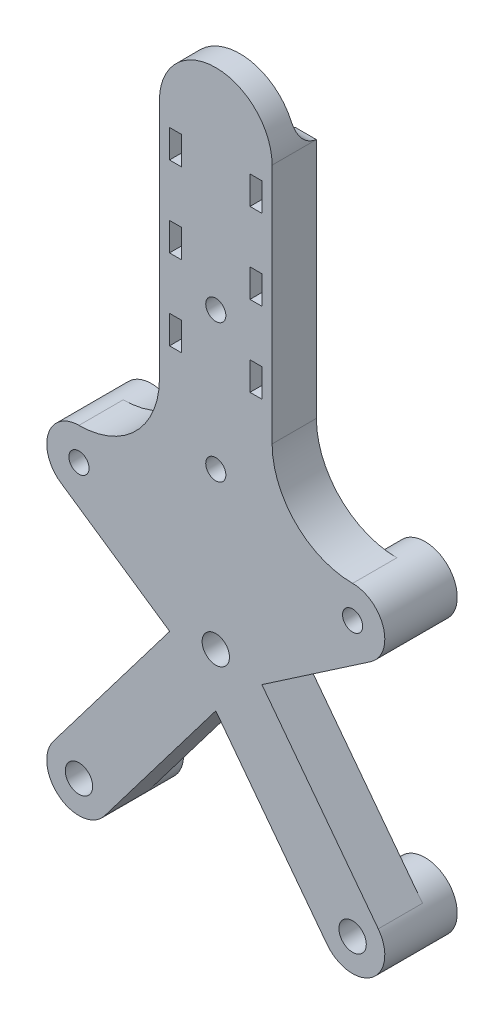
SolidWorks part; units mm, degrees
note: The reader was unsure of these and kept them because the rebuilt part matched: shared geometry of "Sketch1<3>".
ref_plane "Front Plane" through (0, 0, 0) normal (0, 0, 1) x (1, 0, 0)
ref_plane "Top Plane" through (0, 0, 0) normal (0, 1, 0) x (1, 0, 0)
ref_plane "Right Plane" through (0, 0, 0) normal (1, 0, 0) x (0, 0, -1)
sketch "Sketch1" plane through (0, 0, 0) normal (0, 0, 1) x (1, 0, 0)
  line L0 (-17, -11.2005) -> (0, 11.2005) construction
  line L1 (-17, -11.2005) -> (-11.9786, -11.2005) construction
  line L2 (-17, -11.2005) -> (-17, -4.5837) construction
  line L3 (-17, 22.7995) -> (17, 22.7995) construction
  line L4 (17, -11.2005) -> (17, -4.5837) construction
  line L5 (0, 11.2005) -> (-17, 22.7995) construction
  line L6 (17, -11.2005) -> (0, 11.2005) construction
  line L7 (0, 11.2005) -> (17, 22.7995) construction
  line L8 (-13.8137, -13.6186) -> (0, 4.5837)
  line L14 (20.1863, -8.7824) -> (5.7296, 10.2674)
  line L16 (-20.1863, -8.7824) -> (-5.7296, 10.2674)
  line L19 (-17, 26.7995) -> (17, 26.7995)
  line L22 (13.8137, -13.6186) -> (0, 4.5837)
  line L25 (5.7296, 10.2674) -> (19.2544, 19.4953)
  line L26 (17, 17.9571) -> (17, 22.7995) construction
  line L27 (-5.7296, 10.2674) -> (-19.2544, 19.4953)
  line L29 (11.9786, -11.2005) -> (17, -11.2005) construction
  line L30 (3.3084, 13.4578) -> (3.1863, 13.6186)
  line L31 (20.1863, -8.7824) -> (3.1863, 13.6186) construction
  line L34 (-3.3084, 13.4578) -> (-3.1863, 13.6186)
  line L35 (-20.1863, -8.7824) -> (-3.1863, 13.6186) construction
  line L36 (0, 26.7995) -> (0, 66.7995) construction
  line L37 (-13.8137, -13.6186) -> (3.1863, 8.7824) construction
  line L38 (7, 26.7995) -> (7, 66.7995)
  line L39 (13.8137, -13.6186) -> (-3.1863, 8.7824) construction
  line L40 (-7, 26.7995) -> (-7, 66.7995)
  line L41 (-17, 17.9571) -> (-17, 22.7995) construction
  arc A0 (-13.8137, -13.6186) -> (-20.1863, -8.7824) centre (-17, -11.2005) cw
  arc A1 (3.3042, 13.4549) -> (3.1863, 13.6186) centre (0, 11.2005) ccw
  arc A2 (-17, -15.2005) -> (-20.1863, -8.7824) centre (-17, -11.2005) cw
  arc A3 (17, -15.2005) -> (20.1863, -8.7824) centre (17, -11.2005) ccw
  arc A4 (-13.8137, -13.6186) -> (-21, -11.2005) centre (-17, -11.2005) cw
  arc A5 (-14.7456, 26.1037) -> (-21, 22.7995) centre (-17, 22.7995) ccw
  arc A6 (-19.2544, 19.4953) -> (-17, 26.7995) centre (-17, 22.7995) cw
  arc A7 (19.2544, 19.4953) -> (17, 26.7995) centre (17, 22.7995) ccw
  arc A8 (21, -11.2005) -> (13.8137, -13.6186) centre (17, -11.2005) cw
  arc A9 (21, 22.7995) -> (14.7456, 26.1037) centre (17, 22.7995) ccw
  arc A10 (3.1863, 13.6186) -> (3.3042, 13.4549) centre (0, 11.2005) cw
  arc A11 (-14.7456, 26.1037) -> (-19.2544, 19.4953) centre (-17, 22.7995) ccw
  arc A12 (20.1863, -8.7824) -> (13.8137, -13.6186) centre (17, -11.2005) cw
  arc A15 (19.2544, 19.4953) -> (14.7456, 26.1037) centre (17, 22.7995) ccw
  circle A16 centre (-17, -11.2005) radius 4
  arc A17 (-3.3042, 13.4549) -> (-3.1863, 13.6186) centre (0, 11.2005) cw
  arc A18 (-3.1863, 13.6186) -> (-3.3042, 13.4549) centre (0, 11.2005) ccw
  circle A19 centre (17, -11.2005) radius 4
  circle A20 centre (17, 22.7995) radius 4
  circle A21 centre (-17, 22.7995) radius 4
  arc A23 (7, 66.7995) -> (-7, 66.7995) centre (0, 66.7995) ccw
  point P0 (17, -11.2005)
  point P1 (-17, -11.2005)
  point P2 (0, 11.2005)
  point P5 (17, 22.7995)
  point P6 (-17, 22.7995)
  dimension "D6" = 40
  dimension "D7" = 34
  dimension "D8" = 34
  dimension "D2" = 4
  dimension "D3" = 4
  dimension "D4" = 7
  dimension "D5" = 7
  dimension "D1" = 2
extrude "Boss-Extrude1" add sketch "Sketch1" along normal blind 3
extrude "Boss-Extrude2" add sketch "Sketch1<3>" against normal blind 6 contours A6 A21 A5 | A9 A20 A7 | A3 A19 A8 | A0 A16
sketch "Sketch1<3>" plane through (0, 0, 0) normal (0, 0, 1) x (1, 0, 0) same geometry as "Sketch1"
hole_wizard "Tap Drill for M3x0.5 Tap1" positions "Sketch2" profile "Sketch3" hole size "M3x0.5" standard "ANSI Metric"
sketch "Sketch2" plane through (0, 0, -6) normal (0, 0, -1) x (-1, 0, 0)
  point P0 (17, 22.7995)
  point P3 (-17, 22.7995)
sketch "Sketch3" plane through (-17, 22.7995, -6) normal (1, 0, 0) x (0, 1, 0)
  line L0 (0, 0) -> (0, 10.7511)
  line L1 (0, 10.7511) -> (1.25, 10)
  line L2 (1.25, 10) -> (1.25, 0)
  line L5 (1.25, 0) -> (0, 0)
  line L10 (0, 10.7511) -> (-1.25, 10) construction
  line L11 (0, -6.35) -> (0, 107.95) construction
  dimension "Hole Dia." = 2.5
  dimension "Hole Depth" = 10
  dimension "Drill Angle" = 118
hole_wizard "M3 Clearance Hole1" positions "Sketch4" profile "Sketch5" hole size "M3" standard "ANSI Metric"
sketch "Sketch4" plane through (0, 0, -6) normal (0, 0, -1) x (-1, 0, 0)
  point P0 (-17, -11.2005)
  point P3 (17, -11.2005)
sketch "Sketch5" plane through (17, -11.2005, -6) normal (1, 0, 0) x (0, 1, 0)
  line L0 (0, 0) -> (0, 11.0215)
  line L1 (0, 11.0215) -> (1.7, 10)
  line L2 (1.7, 10) -> (1.7, 0)
  line L5 (1.7, 0) -> (0, 0)
  line L10 (0, 11.0215) -> (-1.7, 10) construction
  line L11 (0, -6.35) -> (0, 107.95) construction
  dimension "Hole Dia." = 3.4
  dimension "Hole Depth" = 10
  dimension "Drill Angle" = 118
hole_wizard "M3 Clearance Hole2" positions "Sketch6" profile "Sketch7" hole size "M3" standard "ANSI Metric"
sketch "Sketch6" plane through (0, 0, 3) normal (0, 0, 1) x (1, 0, 0)
  point P0 (0, 11.2005)
sketch "Sketch7" plane through (0, 11.2005, 3) normal (1, 0, 0) x (0, -1, 0)
  line L0 (0, 0) -> (0, 11.0215)
  line L1 (0, 11.0215) -> (1.7, 10)
  line L2 (1.7, 10) -> (1.7, 0)
  line L5 (1.7, 0) -> (0, 0)
  line L10 (0, 11.0215) -> (-1.7, 10) construction
  line L11 (0, -6.35) -> (0, 107.95) construction
  dimension "Hole Dia." = 3.4
  dimension "Hole Depth" = 10
  dimension "Drill Angle" = 118
sketch "Sketch9" plane through (0, 0, 0) normal (0, 0, -1) x (-1, 0, 0)
  line L0 (17, 26.7995) -> (-17, 26.7995) construction
  line L1 (0, 66.7995) -> (4.3656, 66.7995)
  line L2 (0, 66.7995) -> (0, 26.7995)
  line L3 (0, 26.7995) -> (4.3656, 26.7995)
  line L4 (4.3656, 66.7995) -> (4.3656, 26.7995)
  line L6 (0, 66.7995) -> (-4.3656, 66.7995)
  line L7 (0, 66.7995) -> (0, 26.7995)
  line L8 (0, 26.7995) -> (-4.3656, 26.7995)
  line L9 (-4.3656, 66.7995) -> (-4.3656, 26.7995)
  line L10 (-7, 66.7995) -> (7, 66.7995)
  line L11 (-7, 66.7995) -> (-7, 26.7995)
  line L12 (-7, 26.7995) -> (7, 26.7995)
  line L13 (7, 66.7995) -> (7, 26.7995)
  line L20 (0, 4.5837) -> (13.8137, -13.6186)
  line L21 (0, 4.5837) -> (13.8137, -13.6186)
  line L22 (17, 26.7995) -> (7, 26.7995)
  line L23 (7, 26.7995) -> (7, 66.7995)
  line L24 (-7, 66.7995) -> (-7, 26.7995)
  line L25 (-7, 26.7995) -> (-17, 26.7995)
  line L26 (20.1863, -8.7824) -> (5.7296, 10.2674)
  line L27 (20.1863, -8.7824) -> (5.7296, 10.2674)
  line L28 (5.7296, 10.2674) -> (19.2544, 19.4953)
  line L29 (17, 26.7995) -> (7, 26.7995)
  line L30 (7, 26.7995) -> (7, 66.7995)
  line L31 (-7, 66.7995) -> (-7, 26.7995)
  line L32 (-7, 26.7995) -> (-17, 26.7995)
  line L33 (5.7296, 10.2674) -> (19.2544, 19.4953)
  line L37 (-19.2544, 19.4953) -> (-5.7296, 10.2674)
  line L38 (-19.2544, 19.4953) -> (-5.7296, 10.2674)
  line L39 (-5.7296, 10.2674) -> (-20.1863, -8.7824)
  line L40 (-5.7296, 10.2674) -> (-20.1863, -8.7824)
  line L41 (-13.8137, -13.6186) -> (0, 4.5837)
  line L42 (-13.8137, -13.6186) -> (0, 4.5837)
  arc A5 (20.1863, -8.7824) -> (13.8137, -13.6186) centre (17, -11.2005) ccw
  arc A6 (17, 26.7995) -> (19.2544, 19.4953) centre (17, 22.7995) ccw
  arc A7 (7, 66.7995) -> (-7, 66.7995) centre (0, 66.7995) ccw
  arc A8 (-19.2544, 19.4953) -> (-17, 26.7995) centre (-17, 22.7995) ccw
  arc A9 (-13.8137, -13.6186) -> (-20.1863, -8.7824) centre (-17, -11.2005) ccw
  arc A10 (20.1863, -8.7824) -> (13.8137, -13.6186) centre (17, -11.2005) ccw
  arc A11 (17, 26.7995) -> (19.2544, 19.4953) centre (17, 22.7995) ccw
  arc A12 (7, 66.7995) -> (-7, 66.7995) centre (0, 66.7995) ccw
  arc A13 (-19.2544, 19.4953) -> (-17, 26.7995) centre (-17, 22.7995) ccw
  arc A14 (-13.8137, -13.6186) -> (-20.1863, -8.7824) centre (-17, -11.2005) ccw
  dimension "D1" = 4.3656
  dimension "D2" = 4.3656
  dimension "D3" = 0
extrude "Boss-Extrude3" add sketch "Sketch9" along normal blind 2.5
hole_wizard "Tap Drill for M3x0.5 Tap2" positions "Sketch10" profile "Sketch11" hole size "M3x0.5" standard "ANSI Metric"
sketch "Sketch10" plane through (0, 0, 0) normal (0, 0, -1) x (-1, 0, 0)
  line L0 (0, 26.7995) -> (0, 66.7995) construction
  point P0 (0, 30.5825)
  point P5 (0, 47.7293)
sketch "Sketch11" plane through (0, 30.5825, 0) normal (1, 0, 0) x (0, 1, 0)
  line L0 (0, 0) -> (0, 10.7511)
  line L1 (0, 10.7511) -> (1.25, 10)
  line L2 (1.25, 10) -> (1.25, 0)
  line L5 (1.25, 0) -> (0, 0)
  line L10 (0, 10.7511) -> (-1.25, 10) construction
  line L11 (0, -6.35) -> (0, 107.95) construction
  dimension "Hole Dia." = 2.5
  dimension "Hole Depth" = 10
  dimension "Drill Angle" = 118
sketch "Sketch8" plane through (0, 0, 3) normal (0, 0, 1) x (1, 0, 0)
  line L0 (4.25, 44.4793) -> (5.75, 44.4793)
  line L1 (-5.75, 44.4793) -> (-4.25, 44.4793)
  line L2 (-5.75, 44.4793) -> (-5.75, 40.9793)
  line L3 (-5.75, 40.9793) -> (-4.25, 40.9793)
  line L4 (-4.25, 44.4793) -> (-4.25, 40.9793)
  line L5 (5.75, 44.4793) -> (5.75, 40.9793)
  line L6 (4.25, 44.4793) -> (4.25, 40.9793)
  line L7 (4.25, 40.9793) -> (5.75, 40.9793)
  line L8 (4.25, 54.4793) -> (5.75, 54.4793)
  line L9 (5.75, 54.4793) -> (5.75, 50.9793)
  line L10 (4.25, 54.4793) -> (4.25, 50.9793)
  line L11 (4.25, 50.9793) -> (5.75, 50.9793)
  line L12 (-5.75, 54.4793) -> (-4.25, 54.4793)
  line L13 (-4.25, 54.4793) -> (-4.25, 50.9793)
  line L14 (-5.75, 54.4793) -> (-5.75, 50.9793)
  line L15 (-5.75, 50.9793) -> (-4.25, 50.9793)
  line L16 (-7, 26.7995) -> (-7, 66.7995) construction
  line L17 (-5.75, 64.4793) -> (-4.25, 64.4793)
  line L18 (-4.25, 64.4793) -> (-4.25, 60.9793)
  line L19 (-5.75, 64.4793) -> (-5.75, 60.9793)
  line L20 (-5.75, 60.9793) -> (-4.25, 60.9793)
  line L21 (4.25, 64.4793) -> (5.75, 64.4793)
  line L22 (5.75, 64.4793) -> (5.75, 60.9793)
  line L23 (4.25, 64.4793) -> (4.25, 60.9793)
  line L24 (4.25, 60.9793) -> (5.75, 60.9793)
  dimension "D1" = 1.5
  dimension "D2" = 3.5
  dimension "D5" = 1.25
  dimension "D3" = 2
  dimension "D4" = 3
extrude "Cut-Extrude1" cut sketch "Sketch8" against normal blind 15
fillet "Fillet3" radius 3 2 edges at (5.6828, 66.7995, 0) (-5.6828, 66.7995, 0)
fillet "Fillet4" radius 10 2 edges at (7, 26.7995, 0.25) (-7, 26.7995, 0.25)
